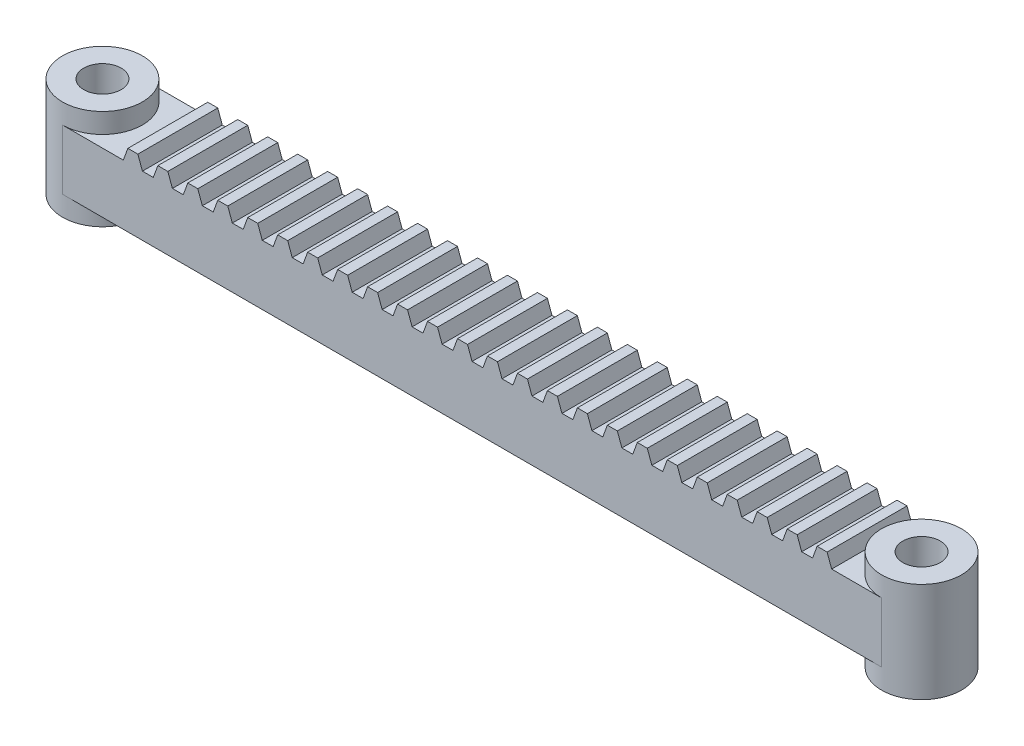
SolidWorks part; units mm, degrees
ref_plane "Front Plane" through (0, 0, 0) normal (0, 0, 1) x (1, 0, 0)
ref_plane "Top Plane" through (0, 0, 0) normal (0, 1, 0) x (1, 0, 0)
ref_plane "Right Plane" through (0, 0, 0) normal (1, 0, 0) x (0, 0, -1)
sketch "Sketch1" plane through (0, 0, 0) normal (0, 0, 1) x (1, 0, 0)
  line L0 (72, 12) -> (71.0901, 14.5)
  line L1 (-82, 12) -> (82, 12)
  line L2 (-82, 12) -> (-82, 0)
  line L3 (-82, 0) -> (82, 0)
  line L4 (82, 12) -> (82, 0)
  line L5 (71.0901, 14.5) -> (69.0901, 14.5)
  line L6 (69.0901, 14.5) -> (68.1801, 12)
  line L7 (70.0901, -10.6775) -> (70.0901, 25.9684) construction
  line L8 (63.0901, 14.5) -> (62.1801, 12)
  line L9 (65.0901, 14.5) -> (63.0901, 14.5)
  line L10 (66, 12) -> (65.0901, 14.5)
  line L11 (57.0901, 14.5) -> (56.1801, 12)
  line L12 (59.0901, 14.5) -> (57.0901, 14.5)
  line L13 (60, 12) -> (59.0901, 14.5)
  line L14 (51.0901, 14.5) -> (50.1801, 12)
  line L15 (53.0901, 14.5) -> (51.0901, 14.5)
  line L16 (54, 12) -> (53.0901, 14.5)
  line L17 (45.0901, 14.5) -> (44.1801, 12)
  line L18 (47.0901, 14.5) -> (45.0901, 14.5)
  line L19 (48, 12) -> (47.0901, 14.5)
  line L20 (39.0901, 14.5) -> (38.1801, 12)
  line L21 (41.0901, 14.5) -> (39.0901, 14.5)
  line L22 (42, 12) -> (41.0901, 14.5)
  line L23 (33.0901, 14.5) -> (32.1801, 12)
  line L24 (35.0901, 14.5) -> (33.0901, 14.5)
  line L25 (36, 12) -> (35.0901, 14.5)
  line L26 (27.0901, 14.5) -> (26.1801, 12)
  line L27 (29.0901, 14.5) -> (27.0901, 14.5)
  line L28 (30, 12) -> (29.0901, 14.5)
  line L29 (21.0901, 14.5) -> (20.1801, 12)
  line L30 (23.0901, 14.5) -> (21.0901, 14.5)
  line L31 (24, 12) -> (23.0901, 14.5)
  line L32 (15.0901, 14.5) -> (14.1801, 12)
  line L33 (17.0901, 14.5) -> (15.0901, 14.5)
  line L34 (18, 12) -> (17.0901, 14.5)
  line L35 (9.0901, 14.5) -> (8.1801, 12)
  line L36 (11.0901, 14.5) -> (9.0901, 14.5)
  line L37 (12, 12) -> (11.0901, 14.5)
  line L38 (3.0901, 14.5) -> (2.1801, 12)
  line L39 (5.0901, 14.5) -> (3.0901, 14.5)
  line L40 (6, 12) -> (5.0901, 14.5)
  line L41 (-2.9099, 14.5) -> (-3.8199, 12)
  line L42 (-0.9099, 14.5) -> (-2.9099, 14.5)
  line L43 (0, 12) -> (-0.9099, 14.5)
  line L44 (-8.9099, 14.5) -> (-9.8199, 12)
  line L45 (-6.9099, 14.5) -> (-8.9099, 14.5)
  line L46 (-6, 12) -> (-6.9099, 14.5)
  line L47 (-14.9099, 14.5) -> (-15.8199, 12)
  line L48 (-12.9099, 14.5) -> (-14.9099, 14.5)
  line L49 (-12, 12) -> (-12.9099, 14.5)
  line L50 (-20.9099, 14.5) -> (-21.8199, 12)
  line L51 (-18.9099, 14.5) -> (-20.9099, 14.5)
  line L52 (-18, 12) -> (-18.9099, 14.5)
  line L53 (-26.9099, 14.5) -> (-27.8199, 12)
  line L54 (-24.9099, 14.5) -> (-26.9099, 14.5)
  line L55 (-24, 12) -> (-24.9099, 14.5)
  line L56 (-32.9099, 14.5) -> (-33.8199, 12)
  line L57 (-30.9099, 14.5) -> (-32.9099, 14.5)
  line L58 (-30, 12) -> (-30.9099, 14.5)
  line L59 (-38.9099, 14.5) -> (-39.8199, 12)
  line L60 (-36.9099, 14.5) -> (-38.9099, 14.5)
  line L61 (-36, 12) -> (-36.9099, 14.5)
  line L62 (-44.9099, 14.5) -> (-45.8199, 12)
  line L63 (-42.9099, 14.5) -> (-44.9099, 14.5)
  line L64 (-42, 12) -> (-42.9099, 14.5)
  line L65 (-50.9099, 14.5) -> (-51.8199, 12)
  line L66 (-48.9099, 14.5) -> (-50.9099, 14.5)
  line L67 (-48, 12) -> (-48.9099, 14.5)
  line L68 (-56.9099, 14.5) -> (-57.8199, 12)
  line L69 (-54.9099, 14.5) -> (-56.9099, 14.5)
  line L70 (-54, 12) -> (-54.9099, 14.5)
  line L71 (-62.9099, 14.5) -> (-63.8199, 12)
  line L72 (-60.9099, 14.5) -> (-62.9099, 14.5)
  line L73 (-60, 12) -> (-60.9099, 14.5)
  line L74 (-68.9099, 14.5) -> (-69.8199, 12)
  line L75 (-66.9099, 14.5) -> (-68.9099, 14.5)
  line L76 (-66, 12) -> (-66.9099, 14.5)
  point P4 (0, 0)
  point P11 (70.0901, 14.5)
  point P13 (0, 0)
  point P106 (0, 0)
  point P107 (0, 0)
  point P108 (0, 0)
  point P109 (0, 0)
  point P110 (0, 0)
  point P111 (0, 0)
  point P112 (0, 0)
  point P113 (0, 0)
  point P114 (0, 0)
  point P115 (0, 0)
  point P116 (0, 0)
  point P117 (0, 0)
  point P118 (0, 0)
  point P119 (0, 0)
  point P120 (0, 0)
  point P121 (0, 0)
  point P122 (0, 0)
  point P123 (0, 0)
  point P124 (0, 0)
  point P125 (0, 0)
  point P126 (0, 0)
  point P127 (0, 0)
  point P128 (0, 0)
  point P129 (0, 0)
  point P130 (0, 0)
  point P131 (0, 0)
  point P132 (0, 0)
  point P133 (0, 0)
  point P134 (0, 0)
  point P135 (0, 0)
  point P136 (0, 0)
  point P137 (0, 0)
  point P138 (0, 0)
  point P139 (0, 0)
  point P140 (0, 0)
  point P141 (0, 0)
  point P142 (0, 0)
  point P143 (0, 0)
  point P144 (0, 0)
  point P145 (0, 0)
  point P146 (0, 0)
  point P147 (0, 0)
  point P148 (0, 0)
  point P149 (0, 0)
  point P150 (0, 0)
  point P151 (0, 0)
  dimension "D1" = 164
  dimension "D2" = 12
  dimension "D3" = 10
  dimension "D4" = 40
  dimension "D5" = 2.5
  dimension "D6" = 2
  dimension "D8" = 6
  dimension "D7" = 24
extrude "Boss-Extrude1" add sketch "Sketch1" along normal blind 16 contours L3 L7 L1 L2 region at (-5.955, 6, 0)
extrude "Boss-Extrude2" add sketch "Sketch1<5>" along normal blind 16 contours L7 L3 L4 L1 | L1 L7 L5 L6 | L7 L1 L0 L5 | L1 L10 L9 L8 | L1 L13 L12 L11 | L1 L16 L15 L14 | L1 L19 L18 L17 | L1 L22 L21 L20 | L1 L25 L24 L23 | L1 L28 L27 L26 | L1 L31 L30 L29 | L1 L34 L33 L32 | L1 L37 L36 L35 | L1 L40 L39 L38 | L1 L43 L42 L41 | L1 L46 L45 L44 | L1 L49 L48 L47 region at (70.8413, 13.1197, 0) region at (76.045, 6, 0) region at (69.3389, 13.1197, 0) region at (64.0901, 13.1197, 0) region at (58.0901, 13.1197, 0) region at (52.0901, 13.1197, 0) region at (46.0901, 13.1197, 0) region at (40.0901, 13.1197, 0) region at (34.0901, 13.1197, 0) region at (28.0901, 13.1197, 0) region at (22.0901, 13.1197, 0) region at (16.0901, 13.1197, 0) region at (10.0901, 13.1197, 0) region at (4.0901, 13.1197, 0) region at (-13.9099, 13.1197, 0) region at (-1.9099, 13.1197, 0) region at (-7.9099, 13.1197, 0)
sketch "Sketch1<5>" plane through (0, 0, 0) normal (0, 0, 1) x (1, 0, 0) same geometry as "Sketch1"
extrude "Boss-Extrude3" add sketch "Sketch1<6>" along normal blind 16 contours L1 L52 L51 L50 | L1 L55 L54 L53 | L1 L58 L57 L56 | L1 L61 L60 L59 | L1 L64 L63 L62 | L1 L67 L66 L65 | L1 L70 L69 L68 | L1 L73 L72 L71 | L1 L76 L75 L74 region at (-67.9099, 13.1197, 0) region at (-61.9099, 13.1197, 0) region at (-55.9099, 13.1197, 0) region at (-49.9099, 13.1197, 0) region at (-43.9099, 13.1197, 0) region at (-37.9099, 13.1197, 0) region at (-31.9099, 13.1197, 0) region at (-25.9099, 13.1197, 0) region at (-19.9099, 13.1197, 0)
sketch "Sketch1<6>" plane through (0, 0, 0) normal (0, 0, 1) x (1, 0, 0) same geometry as "Sketch1"
sketch "Sketch2" plane through (0, 12, 0) normal (0, 1, 0) x (1, 0, 0)
  line L0 (-82, -16) -> (-82, 0) construction
  line L1 (0, 0) -> (0, 31.9164) construction
  line L2 (82, -16) -> (82, 0) construction
  circle A0 centre (-82, -8) radius 8
  circle A1 centre (-82, -8) radius 3.75
  circle A2 centre (82, -8) radius 8
  circle A3 centre (82, -8) radius 3.75
  point P11 (0, 0)
  line M9 (-82, 0) -> (-82, -16)
  dimension "D1" = 16
  dimension "D2" = 7.5
extrude "Boss-Extrude4" add sketch "Sketch2" along normal blind 4 contours A1 A0 M9 | A1 A0 M9 region at (-78.0968, 12, 8) region at (-85.9032, 12, 8)
extrude "Boss-Extrude5" add sketch "Sketch2<3>" against normal blind 16 contours A1 A0 M9 | A1 A0 M9 region at (-78.0968, 12, 8) region at (-85.9032, 12, 8)
sketch "Sketch2<3>" plane through (0, 12, 0) normal (0, 1, 0) x (1, 0, 0) same geometry as "Sketch2"
extrude "Cut-Extrude1" cut sketch "Sketch2<4>" against normal blind 16 contours A1 M9 region at (-80.4085, 12, 8)
sketch "Sketch2<4>" plane through (0, 12, 0) normal (0, 1, 0) x (1, 0, 0) same geometry as "Sketch2"
extrude "Boss-Extrude6" add sketch "Sketch2<5>" against normal blind 16
sketch "Sketch2<5>" plane through (0, 12, 0) normal (0, 1, 0) x (1, 0, 0) same geometry as "Sketch2"
extrude "Boss-Extrude7" add sketch "Sketch2<6>" along normal blind 4
sketch "Sketch2<6>" plane through (0, 12, 0) normal (0, 1, 0) x (1, 0, 0) same geometry as "Sketch2"
extrude "Cut-Extrude2" cut sketch "Sketch2<7>" against normal blind 16 contours A3 region at (82, 12, 8)
sketch "Sketch2<7>" plane through (0, 12, 0) normal (0, 1, 0) x (1, 0, 0) same geometry as "Sketch2"
